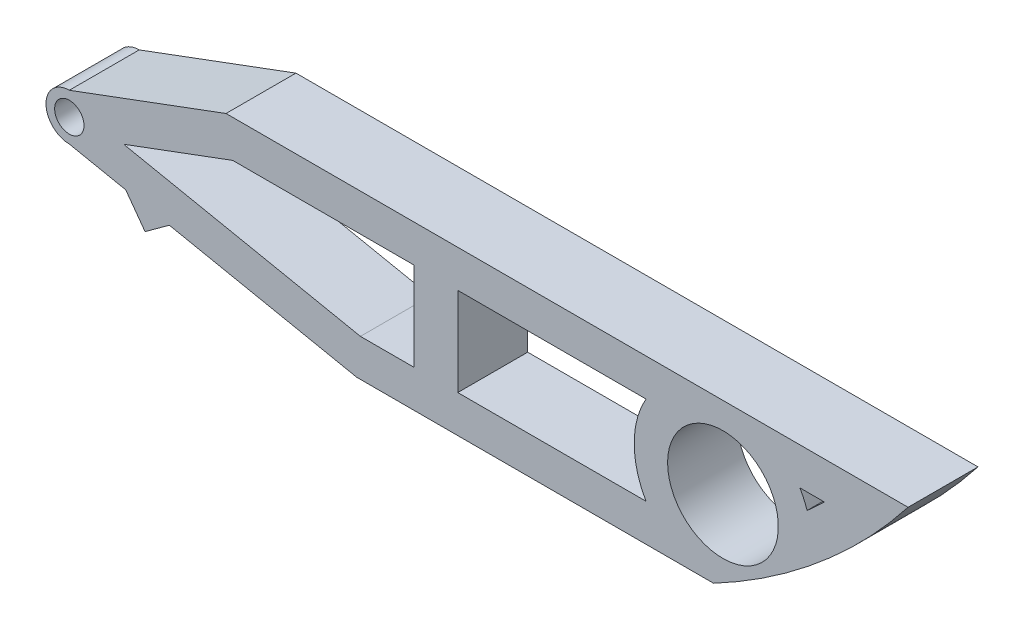
SolidWorks part; units mm, degrees
ref_plane "Front Plane" through (0, 0, 0) normal (0, 0, 1) x (1, 0, 0)
ref_plane "Top Plane" through (0, 0, 0) normal (0, 1, 0) x (1, 0, 0)
ref_plane "Right Plane" through (0, 0, 0) normal (1, 0, 0) x (0, 0, -1)
sketch "Sketch1" plane through (0, 0, 0) normal (0, 0, 1) x (1, 0, 0)
  line L1 (120.65, 22.225) -> (-120.65, 22.225)
  line L2 (120.65, 22.225) -> (120.65, -22.225)
  line L3 (120.65, -22.225) -> (-120.65, -22.225)
  line L4 (-120.65, 22.225) -> (-120.65, -22.225)
  line L5 (120.65, 22.225) -> (-120.65, -22.225) construction
  line L6 (120.65, -22.225) -> (-120.65, 22.225) construction
  point P0 (0, 0)
  dimension "D1" = 241.3
  dimension "D2" = 44.45
extrude "Boss-Extrude1" add sketch "Sketch1" along normal blind 19.06
sketch "Sketch3" plane through (0, 0, 19.06) normal (0, 0, 1) x (1, 0, 0)
  line L0 (0, 0) -> (-120.65, 0) construction
  line L1 (-120.65, 22.225) -> (-120.65, -22.225) construction
  circle A0 centre (-107.95, 0) radius 4
  dimension "D2" = 8
  dimension "D1" = 12.7
extrude "Cut-Extrude1" cut sketch "Sketch3" against normal through all
sketch "Sketch5" plane through (0, 0, 19.06) normal (0, 0, 1) x (1, 0, 0)
  line L0 (-120.65, -22.225) -> (120.65, -22.225) construction
  line L1 (-107.95, -6.35) -> (-29.6229, -22.225)
  line L2 (-107.95, 6.35) -> (-65.2393, 22.225)
  line L3 (120.65, 22.225) -> (-120.65, 22.225) construction
  line L4 (-65.2393, 22.225) -> (-120.65, 22.225)
  line L5 (-120.65, 22.225) -> (-120.65, -22.225)
  line L6 (-120.65, -22.225) -> (-29.6229, -22.225)
  line L7 (120.65, 22.225) -> (120.65, -22.225)
  line L8 (120.65, -22.225) -> (67.6371, -22.225)
  arc A0 (67.6371, -22.225) -> (120.65, 22.225) centre (-9.5799, 123.7049) ccw
  arc A2 (-107.95, 6.35) -> (-107.95, -6.35) centre (-107.95, 0) ccw
  point P15 (-29.6229, -22.225)
  line M3 (-120.65, 22.225) -> (-120.65, -22.225)
  line M4 (-120.65, -22.225) -> (120.65, -22.225)
  line M5 (120.65, -22.225) -> (120.65, 22.225)
  line M6 (120.65, 22.225) -> (-120.65, 22.225)
  dimension "D1" = 165.1
  dimension "D2" = 12.7
extrude "Cut-Extrude2" cut sketch "Sketch5" against normal through all contours A0 L8 M5 | A2 L2 L1 M6 M3 M4 region at (-68.9877, -15.2803, 19.06) region at (104.3043, -8.4634, 19.06)
sketch "Sketch6" plane through (0, 0, 19.06) normal (0, 0, 1) x (1, 0, 0)
  line L0 (-107.95, 0) -> (99.7595, 0) construction
  arc A0 (67.6371, -22.225) -> (120.65, 22.225) centre (-9.5799, 123.7049) ccw construction
  circle A1 centre (19.05, 0) radius 3.1347
  dimension "D1" = 127
sketch "Sketch7" plane through (0, 0, 0) normal (0, 0, -1) x (-1, 0, 0)
  line L0 (44.0204, -2.9977) -> (44.0204, 16.0523) construction
  point P3 (44.0204, -2.9977)
  point P4 (44.0204, 16.0523)
  dimension "D1" = 19.05
sketch "Sketch11" plane through (0, 0, 0) normal (0, 0, -1) x (-1, 0, 0)
  line L1 (107.95, 0) -> (-99.7595, 0) construction
  circle A1 centre (-70.2, 0) radius 15.09
  circle A2 centre (107.95, 0) radius 4 construction
  dimension "D1" = 30.18
  dimension "D2" = 178.15
extrude "Cut-Extrude3" cut sketch "Sketch11" against normal through all
sketch "Sketch12" plane through (0, 0, 0) normal (0, 0, -1) x (-1, 0, 0)
  line L3 (87.2975, -16.6927) -> (80.6869, -11.8756)
  line L4 (107.95, -6.35) -> (29.6229, -22.225) construction
  line L5 (80.6869, -11.8756) -> (92.5615, -9.4689)
  line L6 (92.5615, -9.4689) -> (87.2975, -16.6927)
  dimension "D1" = 90
  dimension "D2" = 8.1795
  dimension "D3" = 137.538
extrude "Boss-Extrude2" add sketch "Sketch12" against normal up to surface (19.06 mm away) up to face at (55.11, 0, 19.06)
sketch "Sketch13" plane through (0, 0, 0) normal (0, 0, -1) x (-1, 0, 0)
  line L0 (-91.178, 12.065) -> (-97.8581, 12.065)
  line L1 (13.9845, -12.065) -> (28.6036, -12.065)
  line L3 (2.0742, -12.065) -> (2.0742, 12.065)
  line L5 (13.9845, -12.065) -> (13.9845, 12.065)
  line L6 (2.0742, 12.065) -> (-49.222, 12.065)
  line L7 (83.0542, -1.0292) -> (86.675, -0.2954)
  line L14 (63.4122, 12.065) -> (-97.8581, 12.065)
  line L15 (-65.0721, -12.065) -> (28.6036, -12.065)
  line L16 (28.6036, -12.065) -> (83.0542, -1.0292)
  line L17 (83.0542, -1.0292) -> (85.0698, -2.498)
  line L18 (85.0698, -2.498) -> (86.675, -0.2954)
  line L19 (86.675, -0.2954) -> (93.1411, 1.0152)
  line L20 (93.1411, 1.0152) -> (63.4122, 12.065)
  line L21 (63.4122, 12.065) -> (13.9845, 12.065)
  line L22 (-49.222, -12.065) -> (2.0742, -12.065)
  line L23 (28.6036, -12.065) -> (83.0542, -1.0292)
  line L26 (86.675, -0.2954) -> (93.1411, 1.0152)
  line L27 (93.1411, 1.0152) -> (63.4122, 12.065)
  arc A0 (-91.178, 12.065) -> (-93.1394, 7.7086) centre (-70.2, 0) ccw
  arc A2 (-49.222, -12.065) -> (-49.222, 12.065) centre (-70.2, 0) ccw
  arc A4 (-97.8581, 12.065) -> (-65.0721, -12.065) centre (9.5799, 123.7049) ccw
  arc A5 (-97.8581, 12.065) -> (-93.1394, 7.7086) centre (9.5799, 123.7049) ccw
  dimension "D1" = 10.16
extrude "Cut-Extrude4" cut sketch "Sketch13" against normal through all
